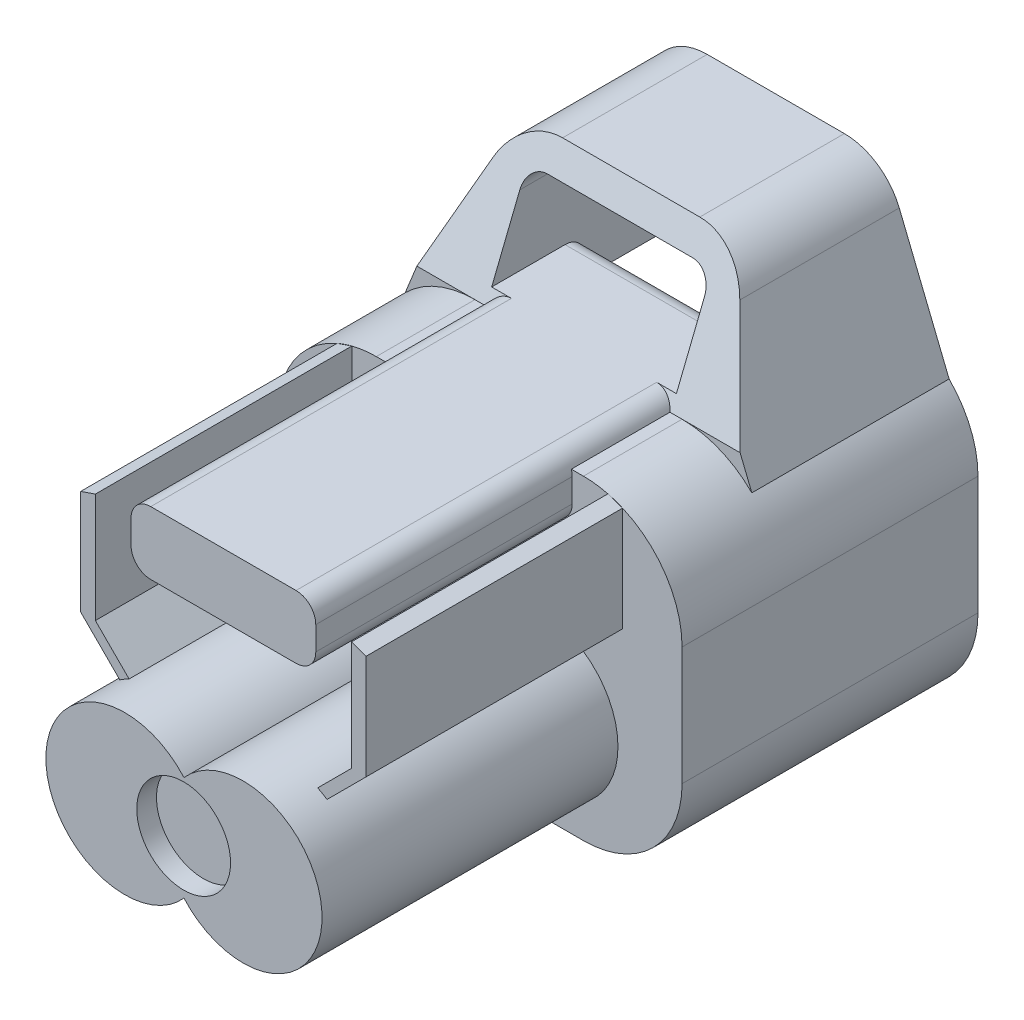
SolidWorks part; units mm, degrees
ref_plane "正面" through (0, 0, 0) normal (0, 0, 1) x (1, 0, 0)
ref_plane "平面" through (0, 0, 0) normal (0, 1, 0) x (1, 0, 0)
ref_plane "右側面" through (0, 0, 0) normal (1, 0, 0) x (0, 0, -1)
sketch "ｽｹｯﾁ1" plane through (0, 0, 0) normal (0, 0, 1) x (1, 0, 0)
  line L1 (5, 0) -> (15.5, 0)
  line L2 (0, 5) -> (0, 11)
  line L3 (5, 16) -> (15.5, 16)
  line L4 (20.5, 5) -> (20.5, 11)
  arc A0 (15.5, 16) -> (20.5, 11) centre (15.5, 11) cw
  arc A1 (15.5, 0) -> (20.5, 5) centre (15.5, 5) ccw
  arc A2 (5, 0) -> (0, 5) centre (5, 5) cw
  arc A3 (0, 11) -> (5, 16) centre (5, 11) cw
  point P7 (20.5, 16)
  point P12 (0, 0)
  point P15 (0, 16)
  dimension "D3" = 5
  dimension "D1" = 20.5
  dimension "D2" = 16
extrude "ﾎﾞｽ - 押し出し1" add sketch "ｽｹｯﾁ1" along normal blind 15
sketch "ｽｹｯﾁ2" plane through (0, 0, 15) normal (0, 0, 1) x (1, 0, 0)
  arc A2 (10.25, 7.6458) -> (10.25, 2.3542) centre (7.25, 5) ccw
  arc A3 (10.25, 7.6458) -> (10.25, 2.3542) centre (13.25, 5) cw
  point P3 (10.3811, 5.8771)
  point P4 (10.25, 5)
  point P5 (10.1189, 5.8771)
  point P6 (7.25, 5)
  point P7 (17.25, 5)
  point P12 (13.25, 5)
extrude "ﾎﾞｽ - 押し出し2" add sketch "ｽｹｯﾁ2" along normal blind 15
sketch "ｽｹｯﾁ3" plane through (0, 0, 15) normal (0, 0, 1) x (1, 0, 0)
  line L0 (5, 8.3072) -> (3.0151, 10.292)
  line L1 (3.0151, 10.292) -> (3.0151, 15.5892)
  line L2 (5.47, 8.5821) -> (3.76, 10.292)
  line L3 (3.76, 10.292) -> (3.76, 15.8438)
  line L4 (3.76, 15.8438) -> (3.0151, 15.5892)
  line L5 (5, 8.3072) -> (5.47, 8.5821)
  line L6 (10.25, 7.6458) -> (10.25, 16) construction
  line L7 (15.5, 16) -> (5, 16) construction
  line L8 (15.5, 8.3072) -> (15.03, 8.5821)
  line L9 (15.03, 8.5821) -> (16.74, 10.292)
  line L10 (15.5, 8.3072) -> (17.4849, 10.292)
  line L11 (16.74, 10.292) -> (16.74, 15.8438)
  line L12 (16.74, 15.8438) -> (17.4849, 15.5892)
  line L13 (17.4849, 10.292) -> (17.4849, 15.5892)
  arc A0 (10.25, 7.6458) -> (10.25, 2.3542) centre (7.25, 5) ccw construction
  arc A1 (5, 16) -> (0, 11) centre (5, 11) ccw construction
extrude "ﾎﾞｽ - 押し出し3" add sketch "ｽｹｯﾁ3" along normal blind 13
sketch "ｽｹｯﾁ4" plane through (0, 0, 0) normal (0, 0, -1) x (-1, 0, 0)
  line L0 (-10.25, 16) -> (-10.25, 0) construction
  line L1 (-15.5, 16) -> (-5, 16) construction
  line L2 (-5, 0) -> (-15.5, 0) construction
  line L3 (-19.0355, 14.5355) -> (-16.5082, 20.7789)
  line L4 (-10.25, 16) -> (-10.25, 23.0115) construction
  line L5 (-13.7274, 22.6532) -> (-6.7726, 22.6532)
  line L6 (-1.4645, 14.5355) -> (-3.9918, 20.7789)
  line L7 (-19.0355, 14.5355) -> (-1.4645, 14.5355)
  arc A0 (-15.5, 16) -> (-20.5, 11) centre (-15.5, 11) ccw construction
  arc A1 (-3.9918, 20.7789) -> (-6.7726, 22.6532) centre (-6.7726, 19.6532) ccw
  arc A2 (-16.5082, 20.7789) -> (-13.7274, 22.6532) centre (-13.7274, 19.6532) cw
  point P15 (-10.25, 22.6532)
  point P17 (-4.7506, 22.6532)
  point P20 (-15.7494, 22.6532)
  dimension "D1" = 3
extrude "ﾎﾞｽ - 押し出し4" add sketch "ｽｹｯﾁ4" against normal blind 10
sketch "ｽｹｯﾁ5" plane through (0, 0, 0) normal (1, 0, 0) x (0, 0, -1)
  line L0 (-10, 16) -> (-7.3282, 22.6532)
  line L1 (-10, 22.6532) -> (0, 22.6532) construction
  line L2 (-7.3282, 22.6532) -> (-10, 22.6532)
  line L3 (-10, 22.6532) -> (-10, 16)
extrude "ｶｯﾄ - 押し出し2" cut sketch "ｽｹｯﾁ5" along normal through all
sketch "ｽｹｯﾁ6" plane through (0, 0, 0) normal (0, 0, -1) x (-1, 0, 0)
  line L0 (-14.9321, 14.7611) -> (-14.9321, 20.2484)
  line L1 (-10.25, 22.6532) -> (-10.25, 11.6201) construction
  line L2 (-6.7726, 22.6532) -> (-13.7274, 22.6532) construction
  line L3 (-5.5679, 14.7611) -> (-5.5679, 20.2484)
  line L4 (-13.9321, 21.2484) -> (-6.5679, 21.2484)
  line L12 (-2.3107, 13.9611) -> (-4.9188, 20.4037)
  line L13 (-6.7726, 21.6532) -> (-13.7274, 21.6532)
  line L14 (-15.5812, 20.4037) -> (-18.1893, 13.9611)
  line L15 (-19.5, 11) -> (-19.5, 5)
  line L16 (-15.5, 1) -> (-5, 1)
  line L17 (-1, 5) -> (-1, 11)
  line L21 (-19.5, 11) -> (-19.5, 5)
  line L22 (-15.5, 1) -> (-5, 1)
  line L23 (-1, 5) -> (-1, 11)
  arc A0 (-5.5679, 20.2484) -> (-6.5679, 21.2484) centre (-6.5679, 20.2484) ccw
  arc A1 (-14.9321, 20.2484) -> (-13.9321, 21.2484) centre (-13.9321, 20.2484) cw
  arc A12 (-1, 11) -> (-2.3107, 13.9611) centre (-5, 11) ccw
  arc A13 (-4.9188, 20.4037) -> (-6.7726, 21.6532) centre (-6.7726, 19.6532) ccw
  arc A14 (-13.7274, 21.6532) -> (-15.5812, 20.4037) centre (-13.7274, 19.6532) ccw
  arc A15 (-18.1893, 13.9611) -> (-19.5, 11) centre (-15.5, 11) ccw
  arc A16 (-19.5, 5) -> (-15.5, 1) centre (-15.5, 5) ccw
  arc A17 (-5, 1) -> (-1, 5) centre (-5, 5) ccw
  arc A18 (-1, 11) -> (-2.3107, 13.9611) centre (-5, 11) ccw
  arc A21 (-18.1893, 13.9611) -> (-19.5, 11) centre (-15.5, 11) ccw
  arc A22 (-19.5, 5) -> (-15.5, 1) centre (-15.5, 5) ccw
  arc A23 (-5, 1) -> (-1, 5) centre (-5, 5) ccw
  spline S0 degree 3 poles (-18.1893, 13.9611) (-17.2661, 14.6327) (-16.0412, 14.7991) (-14.9321, 14.7611) knots 0 0 0 0 1 1 1 1
  spline S1 degree 3 poles (-2.3107, 13.9611) (-3.2339, 14.6327) (-4.4588, 14.7991) (-5.5679, 14.7611) knots 0 0 0 0 1 1 1 1
  point P14 (-5.5679, 21.2484)
  point P18 (-14.9321, 21.2484)
  dimension "D2" = 1
  dimension "D1" = 1
extrude "ｶｯﾄ - 押し出し3" cut sketch "ｽｹｯﾁ6" against normal blind 10
sketch "ｽｹｯﾁ7" plane through (0, 0, 15) normal (0, 0, 1) x (1, 0, 0)
  line L0 (10.25, 7.6458) -> (10.25, 16) construction
  line L1 (15.5, 16) -> (5, 16) construction
  line L2 (5.5679, 16.6985) -> (5.5679, 13.4988)
  line L3 (5.5679, 20.2484) -> (5.5679, 16) construction
  line L4 (5.5679, 16.6985) -> (14.9321, 16.6985)
  line L5 (14.9321, 16) -> (14.9321, 20.2484) construction
  line L6 (14.9321, 16.6985) -> (14.9321, 13.4988)
  line L7 (14.9321, 13.4988) -> (5.5679, 13.4988)
extrude "ﾎﾞｽ - 押し出し5" add sketch "ｽｹｯﾁ7" along normal blind 13 and the other way blind 10
fillet "ﾌｨﾚｯﾄ1" radius 1 7 edges at (10.25, 16.6985, 5) (14.9321, 13.4988, 7.5) (5.5679, 13.4988, 7.5) (5.5679, 13.4988, 21.5) (14.9321, 13.4988, 21.5) (14.9321, 16.6985, 18.8598) (5.5679, 16.6985, 18.8598)
sketch "ｽｹｯﾁ8" plane through (0, 0, 30) normal (0, 0, 1) x (1, 0, 0)
  circle A0 centre (10.2353, 5.0741) radius 2.3777
extrude "ｶｯﾄ - 押し出し4" cut sketch "ｽｹｯﾁ8" against normal blind 1
